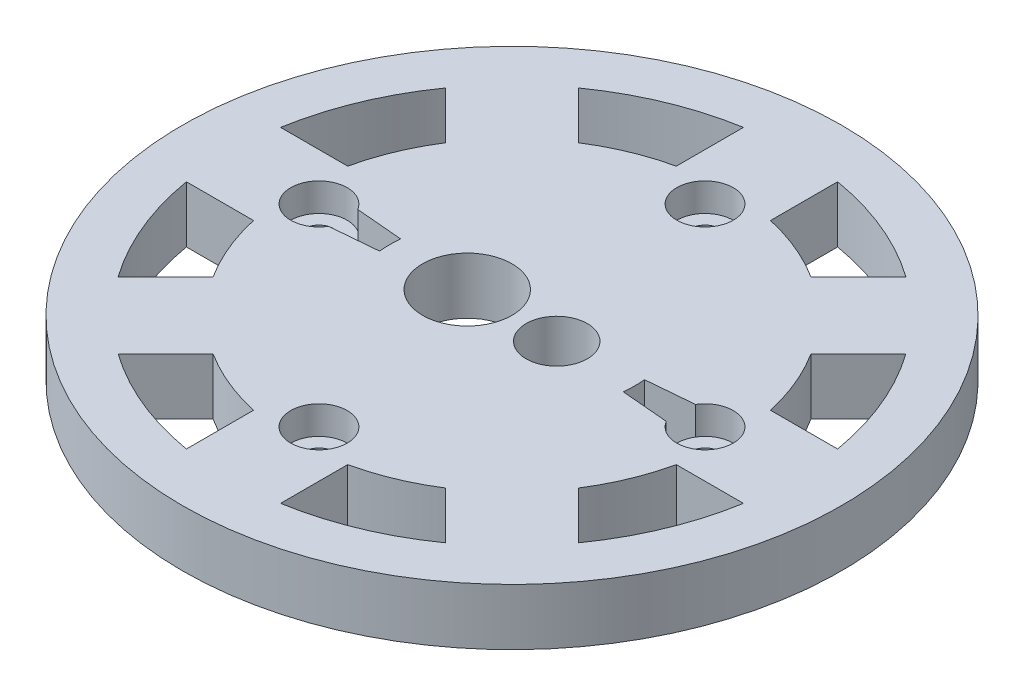
SolidWorks part; units mm, degrees
ref_plane "Front Plane" through (0, 0, 0) normal (0, 0, 1) x (1, 0, 0)
ref_plane "Top Plane" through (0, 0, 0) normal (0, 1, 0) x (1, 0, 0)
ref_plane "Right Plane" through (0, 0, 0) normal (1, 0, 0) x (0, 0, -1)
sketch "Sketch1" plane through (0, 0, 0) normal (0, 1, 0) x (1, 0, 0)
  line L0 (0, 23) -> (0, 18) construction
  line L1 (0, 0) -> (9.5, 0) construction
  line L2 (0, 0) -> (-9.5, 0) construction
  line L3 (5, 29.5804) -> (5, 23.5)
  line L4 (17.381, 24.452) -> (13.0815, 20.1525)
  line L5 (13.0815, 20.1525) -> (12.339, 19.41)
  line L6 (-5, 29.5804) -> (-5, 23.5)
  line L7 (-5, 23.5) -> (-5, 22.4499)
  line L8 (5, 23.5) -> (5, 22.4499)
  line L9 (-5, 29.5804) -> (-5, 22.4499)
  line L10 (20.1525, 13.0815) -> (19.41, 12.339)
  line L11 (24.452, 17.381) -> (20.1525, 13.0815)
  line L12 (5, 29.5804) -> (5, 22.4499)
  line L13 (29.5804, 5) -> (23.5, 5)
  line L14 (23.5, 5) -> (22.4499, 5)
  line L15 (23.5, -5) -> (22.4499, -5)
  line L16 (29.5804, -5) -> (23.5, -5)
  line L17 (24.452, -17.381) -> (20.1525, -13.0815)
  line L18 (20.1525, -13.0815) -> (19.41, -12.339)
  line L19 (13.0815, -20.1525) -> (12.339, -19.41)
  line L20 (17.381, -24.452) -> (13.0815, -20.1525)
  line L21 (5, -29.5804) -> (5, -23.5)
  line L22 (5, -23.5) -> (5, -22.4499)
  line L23 (-5, -23.5) -> (-5, -22.4499)
  line L24 (-5, -29.5804) -> (-5, -23.5)
  line L25 (-17.381, -24.452) -> (-13.0815, -20.1525)
  line L26 (-13.0815, -20.1525) -> (-12.339, -19.41)
  line L27 (-20.1525, -13.0815) -> (-19.41, -12.339)
  line L28 (-24.452, -17.381) -> (-20.1525, -13.0815)
  line L29 (-29.5804, -5) -> (-23.5, -5)
  line L30 (-23.5, -5) -> (-22.4499, -5)
  line L31 (-23.5, 5) -> (-22.4499, 5)
  line L32 (-29.5804, 5) -> (-23.5, 5)
  line L33 (-24.452, 17.381) -> (-20.1525, 13.0815)
  line L34 (-20.1525, 13.0815) -> (-19.41, 12.339)
  line L35 (-13.0815, 20.1525) -> (-12.339, 19.41)
  line L36 (-17.381, 24.452) -> (-13.0815, 20.1525)
  line L37 (-12.9516, 1.1212) -> (-17.9329, 1.5525)
  line L38 (-12.9516, -1.1212) -> (-17.9329, -1.5525)
  line L41 (12.9516, -1.1212) -> (17.9329, -1.5525)
  line L42 (12.9516, 1.1212) -> (17.9329, 1.5525)
  arc A0 (17.9329, 1.5525) -> (1.5525, 17.9329) centre (0, 0) ccw
  arc A1 (-22.9329, -1.7552) -> (-1.7552, -22.9329) centre (0, 0) ccw
  circle A2 centre (0, 20.5) radius 1.5
  circle A3 centre (0, 20.5) radius 3
  circle A4 centre (20.5, 0) radius 3
  circle A5 centre (20.5, 0) radius 1.5
  circle A6 centre (0, -20.5) radius 3
  circle A7 centre (0, -20.5) radius 1.5
  circle A8 centre (-20.5, 0) radius 3
  circle A9 centre (-20.5, 0) radius 1.5
  arc A10 (1.7552, -22.9329) -> (22.9329, -1.7552) centre (0, 0) ccw
  circle A11 centre (0, 0) radius 23 construction
  arc A12 (22.9329, 1.7552) -> (1.7552, 22.9329) centre (0, 0) ccw
  arc A13 (1.5525, -17.9329) -> (17.9329, -1.5525) centre (0, 0) ccw
  circle A14 centre (0, 0) radius 18 construction
  arc A15 (-17.9329, -1.5525) -> (-1.5525, -17.9329) centre (0, 0) ccw
  arc A16 (-1.7552, 22.9329) -> (-22.9329, 1.7552) centre (0, 0) ccw
  arc A17 (-1.5525, 17.9329) -> (-17.9329, 1.5525) centre (0, 0) ccw
  circle A18 centre (4.75, 0) radius 3.25
  circle A19 centre (-4.75, 0) radius 4.75
  circle A20 centre (0, 0) radius 35
  circle A21 centre (0, 0) radius 30
  arc A22 (-1.1212, 12.9516) -> (-12.9516, 1.1212) centre (0, 0) ccw
  arc A23 (-12.9516, -1.1212) -> (-1.1212, -12.9516) centre (0, 0) ccw
  arc A24 (1.1212, -12.9516) -> (12.9516, -1.1212) centre (0, 0) ccw
  arc A25 (12.9516, 1.1212) -> (1.1212, 12.9516) centre (0, 0) ccw
  circle A26 centre (0, 0) radius 13
  point P11 (23, 0)
  point P26 (0, 0)
  point P31 (17.2135, 5.2627)
  point P53 (5, 35)
  point P55 (-5, 35)
  point P101 (0, 0)
  dimension "D1" = 36
  dimension "D3" = 3
  dimension "D7" = 6.5
  dimension "D9" = 70
  dimension "D6" = 9.5
  dimension "D8" = 9.5
  dimension "D2" = 5
  dimension "D4" = 1.5
  dimension "D10" = 8
  dimension "D11" = 5
  dimension "D12" = 5
  dimension "D5" = 4
extrude "Boss-Extrude2" add sketch "Sketch1" along normal blind 6 contours A20 A21 | L32 A21 L29 L30 A1 A8 A16 L31 | L36 A21 L33 L34 A16 L35 | L3 A21 L6 L7 A16 A3 A12 L8 | L11 A21 L4 L5 A12 L10 | L16 A21 L13 L14 A12 A4 A10 L15 | L20 A21 L17 L18 A10 L19 | L24 A21 L21 L22 A10 A6 A1 L23 | L28 A21 L25 L26 A1 L27 | A15 A8 A1 A6 | A17 A3 A16 A8 | A4 A12 A3 A0 | A13 A6 A10 A4 | A26 A23 L38 A15 A6 A13 L41 A24 | A26 A25 L42 A0 A3 A17 L37 A22 | A24 A26 A25 A22 A23 A19 A18 | A8 A9 | A4 A5 region at (0, 0, -26.3927) region at (18.6239, 0, -18.6239) region at (13.5412, 0, -13.5412) region at (-18.6239, 0, -18.6239) region at (26.3927, 0, 0) region at (-13.5412, 0, -13.5412) region at (-26.3927, 0, 0) region at (12.4478, 0, -12.4478) region at (23.274, 0, -0.8962) region at (-17.692, 0, -0.7831) region at (18.6239, 0, 18.6239) region at (-18.6239, 0, 18.6239) region at (0.4195, 0, 0) region at (12.4478, 0, 12.4478) region at (13.5412, 0, 13.5412) region at (-13.5412, 0, 13.5412) region at (0, 0, 26.3927) region at (-34.0101, 0, 0)
extrude "Cut-Extrude3" cut sketch "Sketch1<6>" against normal blind 3 from surface contours A4 A5 | A6 A7 | A8 A9 | A3 A2 region at (2.5952, 0, -21.8278) region at (23.274, 0, -0.8962) region at (-17.692, 0, -0.7831) region at (2.5393, 0, 19.0681) starting at face at (-15.3461, 6, 0)
sketch "Sketch1<6>" plane through (0, 0, 0) normal (0, 1, 0) x (1, 0, 0) same geometry as "Sketch1"
extrude "Boss-Extrude3" add sketch "Sketch1<7>" along normal blind 3 contours A3 A2 | A6 A7 region at (2.5952, 0, -21.8278) region at (2.5393, 0, 19.0681)
sketch "Sketch1<7>" plane through (0, 0, 0) normal (0, 1, 0) x (1, 0, 0) same geometry as "Sketch1"
